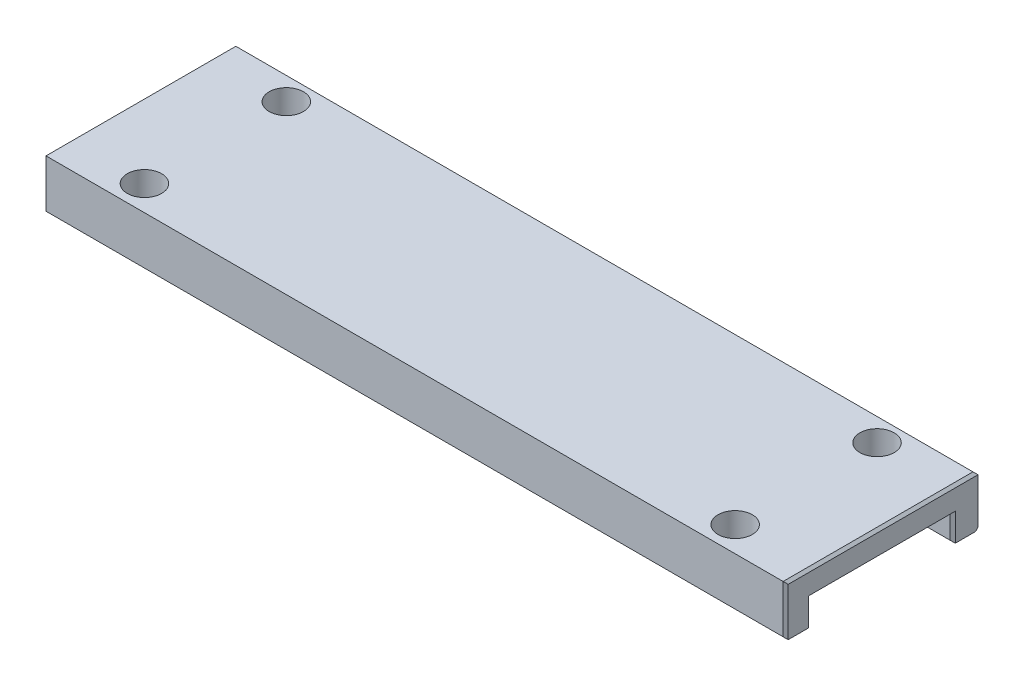
SolidWorks part; units mm, degrees
material "1060 Alloy"
ref_plane "Front Plane" through (0, 0, 0) normal (0, 0, 1) x (1, 0, 0)
ref_plane "Top Plane" through (0, 0, 0) normal (0, 1, 0) x (1, 0, 0)
ref_plane "Right Plane" through (0, 0, 0) normal (1, 0, 0) x (0, 0, -1)
sketch "Sketch1" plane through (0, 0, 0) normal (0, 1, 0) x (1, 0, 0)
  line L1 (-73.5, -19.05) -> (73.5, -19.05)
  line L2 (-73.5, -19.05) -> (-73.5, 19.05)
  line L3 (-73.5, 19.05) -> (73.5, 19.05)
  line L4 (73.5, -19.05) -> (73.5, 19.05)
  line L5 (-73.5, -19.05) -> (73.5, 19.05) construction
  line L6 (-73.5, 19.05) -> (73.5, -19.05) construction
  point P0 (0, 0)
  dimension "D1" = 147
  dimension "D2" = 38.1
extrude "Boss-Extrude1" add sketch "Sketch1" along normal mid plane 10
sketch "Sketch2" plane through (0, 0, 0) normal (1, 0, 0) x (0, 0, -1)
  line L0 (-14.05, 0) -> (14.05, 0)
  line L1 (14.05, 0) -> (14.05, -5)
  line L2 (-19.05, -5) -> (19.05, -5) construction
  line L3 (-14.05, -5) -> (-14.05, 0)
  line L4 (-19.05, 5) -> (-19.05, -5) construction
  line L5 (-14.05, -5) -> (14.05, -5)
  dimension "D1" = 5
extrude "Cut-Extrude1" cut sketch "Sketch2" against normal through all both and the other way through all
hole_wizard "Tap Drill for M8x1.25 Tap1" positions "Sketch4" profile "Sketch3" hole size "M8x1.25" standard "ANSI Metric"
sketch "Sketch4" plane through (0, 5, 0) normal (0, 1, 0) x (1, 0, 0)
  line L2 (73.5, 19.05) -> (-73.5, 19.05) construction
  line L3 (-73.5, 19.05) -> (-73.5, -19.05) construction
  line L4 (-73.5, -19.05) -> (73.5, -19.05) construction
  line L5 (73.5, -19.05) -> (73.5, 19.05) construction
  point P0 (-58.5, 14.05)
  point P2 (58.5, 14.05)
  point P4 (58.5, -14.05)
  point P6 (-58.5, -14.05)
  dimension "D1" = 5
  dimension "D2" = 15
  dimension "D3" = 15
  dimension "D4" = 5
  dimension "D5" = 5
  dimension "D6" = 15
  dimension "D7" = 15
  dimension "D8" = 5
sketch "Sketch3" plane through (-58.5, 5, -14.05) normal (1, 0, 0) x (0, 0, 1)
  line L0 (0, 0) -> (0, 14.0429)
  line L1 (0, 14.0429) -> (3.4, 12)
  line L2 (3.4, 12) -> (3.4, 0)
  line L5 (3.4, 0) -> (0, 0)
  line L10 (0, 14.0429) -> (-3.4, 12) construction
  line L11 (0, -6.35) -> (0, 107.95) construction
  dimension "Hole Dia." = 6.8
  dimension "Hole Depth" = 12
  dimension "Drill Angle" = 118
cosmetic thread "Cosmetic Thread1" parameters "D2"=8
cosmetic thread "Cosmetic Thread2" parameters "D2"=8
cosmetic thread "Cosmetic Thread3" parameters "D2"=8
cosmetic thread "Cosmetic Thread4" parameters "D2"=8
sketch "Sketch5" plane through (0, 0, 0) normal (0, -1, 0) x (1, 0, 0)
  line L0 (-73.5, 14.05) -> (-61.9, 14.05) construction
  line L1 (-64.4, 14.05) -> (-61.9, 14.05)
  line L2 (-55.1, 14.05) -> (-52.6, 14.05)
  line L4 (-73.5, -14.05) -> (-61.9, -14.05) construction
  line L5 (-55.1, -14.05) -> (55.1, -14.05) construction
  line L6 (-64.4, -14.05) -> (-61.9, -14.05)
  line L7 (-55.1, -14.05) -> (-52.6, -14.05)
  line L8 (52.6, -14.05) -> (55.1, -14.05)
  line L9 (61.9, -14.05) -> (64.4, -14.05)
  line L10 (-55.1, 14.05) -> (55.1, 14.05) construction
  line L11 (61.9, 14.05) -> (73.5, 14.05) construction
  line L12 (52.6, 14.05) -> (55.1, 14.05)
  line L13 (61.9, 14.05) -> (64.4, 14.05)
  arc A0 (-61.9, 14.05) -> (-55.1, 14.05) centre (-58.5, 14.05) ccw
  arc A1 (-64.4, 14.05) -> (-52.6, 14.05) centre (-58.5, 14.05) ccw
  arc A2 (-61.9, -14.05) -> (-55.1, -14.05) centre (-58.5, -14.05) cw
  arc A3 (-64.4, -14.05) -> (-52.6, -14.05) centre (-58.5, -14.05) cw
  arc A4 (55.1, -14.05) -> (61.9, -14.05) centre (58.5, -14.05) cw
  arc A5 (52.6, -14.05) -> (64.4, -14.05) centre (58.5, -14.05) cw
  arc A6 (55.1, 14.05) -> (61.9, 14.05) centre (58.5, 14.05) ccw
  arc A7 (52.6, 14.05) -> (64.4, 14.05) centre (58.5, 14.05) ccw
  dimension "D1" = 3.4
  dimension "D2" = 2.5
  dimension "D3" = 3.4
  dimension "D4" = 2.5
  dimension "D5" = 3.4
  dimension "D6" = 2.5
  dimension "D7" = 3.4
  dimension "D8" = 2.5
extrude "Boss-Extrude2" add sketch "Sketch5" along normal up to surface (5 mm away) up to face at (0, -5, 16.15)
chamfer "Chamfer1" distance 0.5 angle 45 23 edges at (-73.5, 5, 0) (-73.5, 0, 19.05) (-73.5, -2.5, 14.05) (-73.5, 0, 0) (-73.5, -2.5, -14.05) (0, -5, 19.05) (73.5, 0, 19.05) (-68.95, -5, 14.05) (-58.5, -5, 8.15) (0, -5, 14.05) (58.5, -5, 8.15) (68.95, -5, 14.05) (73.5, -2.5, 14.05) (73.5, 0, 0) (73.5, -2.5, -14.05) (73.5, 5, 0) (0, 5, -19.05) (-68.95, -5, -14.05) (-58.5, -5, -8.15) (0, -5, -14.05) (58.5, -5, -8.15) (68.95, -5, -14.05) (0, -5, -19.05)
